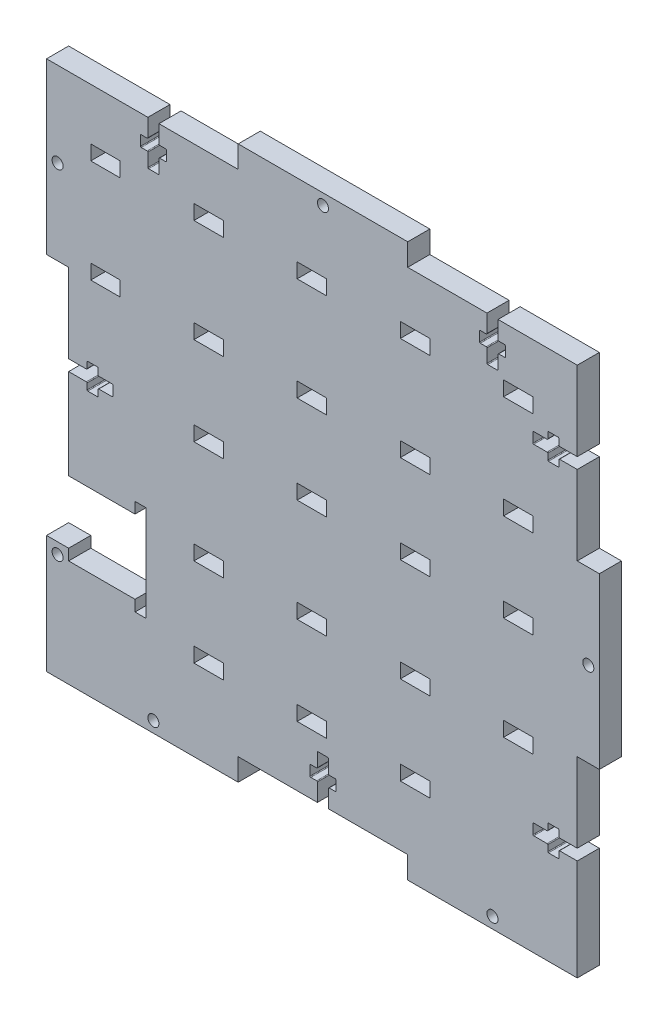
SolidWorks part; units mm, degrees
ref_plane "Front Plane" through (0, 0, 0) normal (0, 0, 1) x (1, 0, 0)
ref_plane "Top Plane" through (0, 0, 0) normal (0, 1, 0) x (1, 0, 0)
ref_plane "Right Plane" through (0, 0, 0) normal (1, 0, 0) x (0, 0, -1)
sketch "Sketch1" plane through (0, 0, 0) normal (0, 0, 1) x (1, 0, 0)
  line L0 (-69, 69) -> (-23, 69)
  line L5 (-75, -75) -> (75, -75) construction
  line L6 (-75, -75) -> (-75, 75) construction
  line L7 (-75, 75) -> (75, 75) construction
  line L8 (75, -75) -> (75, 75) construction
  line L9 (75, 23) -> (69, 23)
  line L10 (69, -23) -> (75, -23)
  line L11 (-69, -69) -> (69, -69) construction
  line L12 (-69, -69) -> (-69, 69) construction
  line L13 (-69, 69) -> (69, 69) construction
  line L14 (69, -69) -> (69, 69) construction
  line L15 (-69, -69) -> (69, 69) construction
  line L16 (69, -69) -> (69, -23)
  line L17 (-23, 69) -> (-23, 75)
  line L18 (-23, 75) -> (23, 75)
  line L19 (23, 75) -> (23, 69)
  line L20 (23, 69) -> (69, 69)
  line L21 (75, -23) -> (75, 23)
  line L22 (69, 23) -> (69, 69)
  line L23 (-75, 23) -> (-69, 23)
  line L24 (-69, 69) -> (-75, 69)
  line L25 (-75, 69) -> (-75, 23)
  line L26 (69, -69) -> (69, -75)
  line L27 (69, -75) -> (23, -75)
  line L28 (23, -75) -> (23, -69)
  line L29 (23, -69) -> (-23, -69)
  line L30 (-23, -69) -> (-23, -75)
  line L31 (-23, -75) -> (-69, -75)
  line L32 (-69, -75) -> (-69, -69) construction
  line L33 (-69, 23) -> (-69, -23)
  line L34 (-69, -23) -> (-75, -23)
  line L35 (-75, -23) -> (-75, -69)
  line L36 (-75, -69) -> (-69, -69) construction
  line L37 (-46, 69) -> (-46, -75) construction
  line L38 (-69, 69) -> (69, -69) construction
  line L39 (-75, -75) -> (-69, -75)
  line L40 (-75, -75) -> (-75, -69)
  point P0 (0, 0)
  point P6 (-7, -7)
  point P26 (0, -75)
  point P27 (-75, 0)
  dimension "D1" = 150
  dimension "D2" = 150
  dimension "D5" = 46
  dimension "D3" = 6
  dimension "D6" = 6
  dimension "D7" = 6
extrude "Box Side" add sketch "Sketch1" along normal blind 6
sketch "Sketch2" plane through (0, 0, 6) normal (0, 0, 1) x (1, 0, 0)
  line L0 (23, 72) -> (-23, 72) construction
  line L1 (23, 75) -> (23, 69) construction
  line L2 (-23, 69) -> (-23, 75) construction
  line L3 (-46, 69) -> (-46, -75) construction
  line L5 (0, 75) -> (0, 69) construction
  line L6 (-23, 75) -> (23, 75) construction
  line L7 (-69, 69) -> (69, 69) construction
  line L16 (-46, 69) -> (-46, -75) construction
  line L21 (0, -69) -> (0, 69) construction
  line L35 (-69, 69) -> (-23, 69) construction
  line L36 (-44.5, 69) -> (-44.5, 64.2)
  line L37 (-44.3, 64) -> (-42.7, 64)
  line L38 (-42.5, 63.8) -> (-42.5, 61.2)
  line L39 (-42.7, 61) -> (-44.3, 61)
  line L40 (-44.5, 60.8) -> (-44.5, 57.2)
  line L46 (-44.7, 57) -> (-47.3, 57)
  line L48 (-44.5, 69) -> (-47.5, 69)
  line L51 (-47.5, 60.8) -> (-47.5, 57.2)
  line L52 (-49.3, 61) -> (-47.7, 61)
  line L53 (-49.5, 63.8) -> (-49.5, 61.2)
  line L54 (-47.7, 64) -> (-49.3, 64)
  line L55 (-47.5, 69) -> (-47.5, 64.2)
  line L56 (47.5, 69) -> (47.5, 64.2)
  line L57 (47.7, 64) -> (49.3, 64)
  line L58 (49.5, 63.8) -> (49.5, 61.2)
  line L59 (49.3, 61) -> (47.7, 61)
  line L60 (47.5, 60.8) -> (47.5, 57.2)
  line L61 (44.5, 69) -> (47.5, 69)
  line L62 (44.7, 57) -> (47.3, 57)
  line L63 (44.5, 60.8) -> (44.5, 57.2)
  line L64 (42.7, 61) -> (44.3, 61)
  line L65 (42.5, 63.8) -> (42.5, 61.2)
  line L66 (44.3, 64) -> (42.7, 64)
  line L67 (44.5, 69) -> (44.5, 64.2)
  line L68 (-69, -69) -> (69, 69) construction
  line L69 (-69, -69) -> (69, 69) construction
  line L70 (75, 0) -> (69, 0) construction
  line L71 (72, 23) -> (72, -23) construction
  line L72 (69, 44.5) -> (64.2, 44.5)
  line L73 (64, 44.3) -> (64, 42.7)
  line L74 (63.8, 42.5) -> (61.2, 42.5)
  line L75 (61, 42.7) -> (61, 44.3)
  line L76 (60.8, 44.5) -> (57.2, 44.5)
  line L77 (57, 44.7) -> (57, 47.3)
  line L78 (69, 44.5) -> (69, 47.5)
  line L79 (60.8, 47.5) -> (57.2, 47.5)
  line L80 (61, 49.3) -> (61, 47.7)
  line L81 (63.8, 49.5) -> (61.2, 49.5)
  line L82 (64, 47.7) -> (64, 49.3)
  line L83 (69, 47.5) -> (64.2, 47.5)
  line L84 (69, -47.5) -> (64.2, -47.5)
  line L85 (64, -47.7) -> (64, -49.3)
  line L86 (63.8, -49.5) -> (61.2, -49.5)
  line L87 (61, -49.3) -> (61, -47.7)
  line L88 (60.8, -47.5) -> (57.2, -47.5)
  line L89 (69, -44.5) -> (69, -47.5)
  line L90 (57, -44.7) -> (57, -47.3)
  line L91 (60.8, -44.5) -> (57.2, -44.5)
  line L92 (61, -42.7) -> (61, -44.3)
  line L93 (63.8, -42.5) -> (61.2, -42.5)
  line L94 (64, -44.3) -> (64, -42.7)
  line L95 (69, -44.5) -> (64.2, -44.5)
  line L120 (-69, 69) -> (69, -69) construction
  line L121 (-69, 69) -> (69, -69) construction
  line L122 (-1.5, -69) -> (1.5, -69)
  line L123 (-23, -69) -> (23, -69) construction
  line L124 (1.5, -69) -> (1.5, -64.2)
  line L125 (1.7, -64) -> (3.3, -64)
  line L126 (3.5, -63.8) -> (3.5, -61.2)
  line L127 (3.3, -61) -> (1.7, -61)
  line L128 (1.5, -60.8) -> (1.5, -57.2)
  line L129 (1.3, -57) -> (-1.3, -57)
  line L130 (-1.5, -60.8) -> (-1.5, -57.2)
  line L131 (-3.3, -61) -> (-1.7, -61)
  line L132 (-3.5, -63.8) -> (-3.5, -61.2)
  line L133 (-1.7, -64) -> (-3.3, -64)
  line L134 (-1.5, -69) -> (-1.5, -64.2)
  line L135 (-69, -1.5) -> (-64.2, -1.5)
  line L136 (-64, -1.7) -> (-64, -3.3)
  line L137 (-63.8, -3.5) -> (-61.2, -3.5)
  line L138 (-61, -3.3) -> (-61, -1.7)
  line L139 (-60.8, -1.5) -> (-57.2, -1.5)
  line L140 (-57, 1.3) -> (-57, -1.3)
  line L141 (-60.8, 1.5) -> (-57.2, 1.5)
  line L142 (-61, 3.3) -> (-61, 1.7)
  line L143 (-63.8, 3.5) -> (-61.2, 3.5)
  line L144 (-64, 1.7) -> (-64, 3.3)
  line L145 (-69, 1.5) -> (-64.2, 1.5)
  line L146 (-69, -1.5) -> (-69, 1.5)
  line L147 (-69, -72) -> (-23, -72) construction
  line L148 (-23, 69) -> (-75, 69) construction
  line L149 (-23, -75) -> (-23, -69) construction
  line L150 (-69, -69) -> (-69, -75) construction
  line L151 (-75, -75) -> (-23, -75) construction
  circle A0 centre (0, 72) radius 1.5
  arc A1 (-44.5, 57.2) -> (-44.7, 57) centre (-44.7, 57.2) cw
  arc A2 (-44.3, 61) -> (-44.5, 60.8) centre (-44.3, 60.8) ccw
  arc A3 (-42.5, 61.2) -> (-42.7, 61) centre (-42.7, 61.2) cw
  arc A4 (-42.7, 64) -> (-42.5, 63.8) centre (-42.7, 63.8) cw
  arc A5 (-44.5, 64.2) -> (-44.3, 64) centre (-44.3, 64.2) ccw
  arc A6 (-47.5, 64.2) -> (-47.7, 64) centre (-47.7, 64.2) cw
  arc A7 (-49.3, 64) -> (-49.5, 63.8) centre (-49.3, 63.8) ccw
  arc A8 (-49.5, 61.2) -> (-49.3, 61) centre (-49.3, 61.2) ccw
  arc A9 (-47.7, 61) -> (-47.5, 60.8) centre (-47.7, 60.8) cw
  arc A10 (-47.5, 57.2) -> (-47.3, 57) centre (-47.3, 57.2) ccw
  arc A11 (47.5, 57.2) -> (47.3, 57) centre (47.3, 57.2) cw
  arc A12 (47.7, 61) -> (47.5, 60.8) centre (47.7, 60.8) ccw
  arc A13 (49.5, 61.2) -> (49.3, 61) centre (49.3, 61.2) cw
  arc A14 (49.3, 64) -> (49.5, 63.8) centre (49.3, 63.8) cw
  arc A15 (47.5, 64.2) -> (47.7, 64) centre (47.7, 64.2) ccw
  arc A16 (44.5, 64.2) -> (44.3, 64) centre (44.3, 64.2) cw
  arc A17 (42.7, 64) -> (42.5, 63.8) centre (42.7, 63.8) ccw
  arc A18 (42.5, 61.2) -> (42.7, 61) centre (42.7, 61.2) ccw
  arc A19 (44.3, 61) -> (44.5, 60.8) centre (44.3, 60.8) cw
  arc A20 (44.5, 57.2) -> (44.7, 57) centre (44.7, 57.2) ccw
  arc A21 (57.2, 44.5) -> (57, 44.7) centre (57.2, 44.7) cw
  arc A22 (61, 44.3) -> (60.8, 44.5) centre (60.8, 44.3) ccw
  arc A23 (61.2, 42.5) -> (61, 42.7) centre (61.2, 42.7) cw
  arc A24 (64, 42.7) -> (63.8, 42.5) centre (63.8, 42.7) cw
  arc A25 (64.2, 44.5) -> (64, 44.3) centre (64.2, 44.3) ccw
  arc A26 (64.2, 47.5) -> (64, 47.7) centre (64.2, 47.7) cw
  arc A27 (64, 49.3) -> (63.8, 49.5) centre (63.8, 49.3) ccw
  arc A28 (61.2, 49.5) -> (61, 49.3) centre (61.2, 49.3) ccw
  arc A29 (61, 47.7) -> (60.8, 47.5) centre (60.8, 47.7) cw
  arc A30 (57.2, 47.5) -> (57, 47.3) centre (57.2, 47.3) ccw
  arc A31 (57.2, -47.5) -> (57, -47.3) centre (57.2, -47.3) cw
  arc A32 (61, -47.7) -> (60.8, -47.5) centre (60.8, -47.7) ccw
  arc A33 (61.2, -49.5) -> (61, -49.3) centre (61.2, -49.3) cw
  arc A34 (64, -49.3) -> (63.8, -49.5) centre (63.8, -49.3) cw
  arc A35 (64.2, -47.5) -> (64, -47.7) centre (64.2, -47.7) ccw
  arc A36 (64.2, -44.5) -> (64, -44.3) centre (64.2, -44.3) cw
  arc A37 (64, -42.7) -> (63.8, -42.5) centre (63.8, -42.7) ccw
  arc A38 (61.2, -42.5) -> (61, -42.7) centre (61.2, -42.7) ccw
  arc A39 (61, -44.3) -> (60.8, -44.5) centre (60.8, -44.3) cw
  arc A40 (57.2, -44.5) -> (57, -44.7) centre (57.2, -44.7) ccw
  circle A41 centre (72, 0) radius 1.5
  arc A62 (1.5, -57.2) -> (1.3, -57) centre (1.3, -57.2) ccw
  arc A63 (1.7, -61) -> (1.5, -60.8) centre (1.7, -60.8) cw
  arc A64 (3.5, -61.2) -> (3.3, -61) centre (3.3, -61.2) ccw
  arc A65 (3.3, -64) -> (3.5, -63.8) centre (3.3, -63.8) ccw
  arc A66 (1.5, -64.2) -> (1.7, -64) centre (1.7, -64.2) cw
  arc A67 (-1.5, -64.2) -> (-1.7, -64) centre (-1.7, -64.2) ccw
  arc A68 (-3.3, -64) -> (-3.5, -63.8) centre (-3.3, -63.8) cw
  arc A69 (-3.5, -61.2) -> (-3.3, -61) centre (-3.3, -61.2) cw
  arc A70 (-1.7, -61) -> (-1.5, -60.8) centre (-1.7, -60.8) ccw
  arc A71 (-1.5, -57.2) -> (-1.3, -57) centre (-1.3, -57.2) cw
  arc A72 (-57.2, -1.5) -> (-57, -1.3) centre (-57.2, -1.3) ccw
  arc A73 (-61, -1.7) -> (-60.8, -1.5) centre (-60.8, -1.7) cw
  arc A74 (-61.2, -3.5) -> (-61, -3.3) centre (-61.2, -3.3) ccw
  arc A75 (-64, -3.3) -> (-63.8, -3.5) centre (-63.8, -3.3) ccw
  arc A76 (-64.2, -1.5) -> (-64, -1.7) centre (-64.2, -1.7) cw
  arc A77 (-64.2, 1.5) -> (-64, 1.7) centre (-64.2, 1.7) ccw
  arc A78 (-64, 3.3) -> (-63.8, 3.5) centre (-63.8, 3.3) cw
  arc A79 (-61.2, 3.5) -> (-61, 3.3) centre (-61.2, 3.3) cw
  arc A80 (-61, 1.7) -> (-60.8, 1.5) centre (-60.8, 1.7) ccw
  arc A81 (-57.2, 1.5) -> (-57, 1.3) centre (-57.2, 1.3) cw
  circle A82 centre (-46, -72) radius 1.5
  circle A83 centre (46, -72) radius 1.5
  circle A84 centre (-72, 46) radius 1.5
  circle A85 centre (-72, -46) radius 1.5
  point P6 (0, 72)
  point P38 (0, 0)
  point P56 (-46, 57)
  point P88 (46, 57)
  point P161 (57, 46)
  point P162 (57, -46)
  point P198 (0, -57)
  point P231 (-57, 0)
  point P234 (-42.5, 62.5)
  dimension "D1" = 3
  dimension "D2" = 0.2
  dimension "D8" = 0.2
  dimension "D14" = 3
  dimension "D4" = 3
  dimension "D7" = 1.5
  dimension "D10" = 3
  dimension "D12" = 1.5
  dimension "D9" = 12
  dimension "D11" = 5
  dimension "D13" = 7
  dimension "D3" = 12
  dimension "D5" = 7
  dimension "D6" = 5
extrude "Screw Cut-outs" cut sketch "Sketch2" against normal through all
sketch "Sketch3" plane through (0, 0, 6) normal (0, 0, 1) x (1, 0, 0)
  line L0 (-75, -75) -> (-23, -75) construction
  line L1 (-75, -49) -> (-48, -49)
  line L2 (-75, -49) -> (-75, -23)
  line L3 (-75, -23) -> (-48, -23)
  line L4 (-48, -49) -> (-48, -23)
  line L5 (-75, -23) -> (-75, -75) construction
  line L6 (-75, -46) -> (-48, -46)
  line L7 (-75, -26) -> (-48, -26)
  line L9 (-75, -26) -> (-69, -26)
  line L10 (-75, -26) -> (-75, -29)
  line L11 (-75, -29) -> (-69, -29)
  line L12 (-69, -26) -> (-69, -29)
  line L13 (-75, -46) -> (-69, -46)
  line L14 (-75, -46) -> (-75, -43)
  line L15 (-75, -43) -> (-69, -43)
  line L16 (-69, -46) -> (-69, -43)
  line L17 (-69, -26) -> (-75, -26)
  line L18 (-69, -26) -> (-69, -23)
  line L19 (-69, -23) -> (-75, -23)
  line L20 (-75, -26) -> (-75, -23)
  line L25 (-48, -23) -> (-51, -23)
  line L26 (-48, -23) -> (-48, -26)
  line L27 (-48, -26) -> (-51, -26)
  line L28 (-51, -23) -> (-51, -26)
  line L29 (-48, -46) -> (-51, -46)
  line L30 (-48, -46) -> (-48, -49)
  line L31 (-48, -49) -> (-51, -49)
  line L32 (-51, -46) -> (-51, -49)
  dimension "D1" = 26
  dimension "D2" = 27
  dimension "D3" = 26
  dimension "D4" = 20
  dimension "D5" = 3
  dimension "D6" = 3
  dimension "D7" = 6
  dimension "D8" = 3
  dimension "D9" = 3
extrude "Cut-Extrude1" cut sketch "Sketch3" against normal through all contours L7 L2 L6 L4 | L10 L9 L12 L11 | L18 L17 L20 L19 | L26 L25 L28 L27 | L30 L29 L32 L31 region at (-60.75, -36, 6)
sketch "Sketch4" plane through (0, 0, 6) normal (0, 0, 1) x (1, 0, 0)
  line L0 (-27, 55) -> (-27, 51)
  line L1 (-63, 55) -> (-55, 55)
  line L2 (-63, 55) -> (-63, 51)
  line L3 (-63, 51) -> (-55, 51)
  line L4 (-55, 55) -> (-55, 51)
  line L5 (-59, 53) -> (-31, 53) construction
  line L6 (-59, 53) -> (-59, 25) construction
  line L7 (-59, 25) -> (-31, 25) construction
  line L8 (-31, 53) -> (-31, 25) construction
  line L9 (-59, 53) -> (-31, 25) construction
  line L10 (-59, 25) -> (-31, 53) construction
  line L11 (-35, 55) -> (-27, 55)
  line L12 (-35, 55) -> (-35, 51)
  line L13 (-35, 51) -> (-27, 51)
  line L14 (-27, 27) -> (-27, 23)
  line L15 (-35, 27) -> (-27, 27)
  line L16 (-35, 27) -> (-35, 23)
  line L17 (-35, 23) -> (-27, 23)
  line L18 (-55, 27) -> (-55, 23)
  line L19 (-63, 27) -> (-55, 27)
  line L20 (-63, 27) -> (-63, 23)
  line L21 (-63, 23) -> (-55, 23)
  line L22 (-47.5, 69) -> (-75, 69) construction
  line L23 (-75, 69) -> (-75, 23) construction
  line L24 (21, 23.2836) -> (29, 23.2836)
  line L25 (21, 27.2836) -> (29, 27.2836)
  line L26 (21, 27.2836) -> (21, 23.2836)
  line L27 (29, 27.2836) -> (29, 23.2836)
  line L28 (1, 27.2836) -> (1, 23.2836)
  line L29 (-7, 23.2836) -> (1, 23.2836)
  line L30 (-7, 27.2836) -> (-7, 23.2836)
  line L31 (-7, 27.2836) -> (1, 27.2836)
  line L32 (-7, 51.2836) -> (1, 51.2836)
  line L33 (-7, 55.2836) -> (-7, 51.2836)
  line L34 (-7, 55.2836) -> (1, 55.2836)
  line L35 (1, 55.2836) -> (1, 51.2836)
  line L36 (29, 55.2836) -> (29, 51.2836)
  line L37 (21, 51.2836) -> (29, 51.2836)
  line L38 (21, 55.2836) -> (29, 55.2836)
  line L39 (21, 55.2836) -> (21, 51.2836)
  line L44 (57, 27.5671) -> (57, 23.5671)
  line L45 (49, 23.5671) -> (57, 23.5671)
  line L46 (49, 27.5671) -> (49, 23.5671)
  line L47 (49, 27.5671) -> (57, 27.5671)
  line L48 (49, 51.5671) -> (57, 51.5671)
  line L49 (49, 55.5671) -> (49, 51.5671)
  line L50 (49, 55.5671) -> (57, 55.5671)
  line L51 (57, 55.5671) -> (57, 51.5671)
  line L56 (21, -28.7164) -> (29, -28.7164)
  line L57 (21, -24.7164) -> (29, -24.7164)
  line L58 (21, -24.7164) -> (21, -28.7164)
  line L59 (29, -24.7164) -> (29, -28.7164)
  line L60 (1, -24.7164) -> (1, -28.7164)
  line L61 (-7, -28.7164) -> (1, -28.7164)
  line L62 (-7, -24.7164) -> (-7, -28.7164)
  line L63 (-7, -24.7164) -> (1, -24.7164)
  line L64 (-7, -0.7164) -> (1, -0.7164)
  line L65 (-7, 3.2836) -> (-7, -0.7164)
  line L66 (-7, 3.2836) -> (1, 3.2836)
  line L67 (1, 3.2836) -> (1, -0.7164)
  line L68 (29, 3.2836) -> (29, -0.7164)
  line L69 (21, -0.7164) -> (29, -0.7164)
  line L70 (21, 3.2836) -> (29, 3.2836)
  line L71 (21, 3.2836) -> (21, -0.7164)
  line L76 (57, -24.4329) -> (57, -28.4329)
  line L77 (49, -28.4329) -> (57, -28.4329)
  line L78 (49, -24.4329) -> (49, -28.4329)
  line L79 (49, -24.4329) -> (57, -24.4329)
  line L80 (49, -0.4329) -> (57, -0.4329)
  line L81 (49, 3.5671) -> (49, -0.4329)
  line L82 (49, 3.5671) -> (57, 3.5671)
  line L83 (57, 3.5671) -> (57, -0.4329)
  line L96 (-7, -52.7164) -> (1, -52.7164)
  line L97 (-7, -48.7164) -> (-7, -52.7164)
  line L98 (-7, -48.7164) -> (1, -48.7164)
  line L99 (1, -48.7164) -> (1, -52.7164)
  line L100 (29, -48.7164) -> (29, -52.7164)
  line L101 (21, -52.7164) -> (29, -52.7164)
  line L102 (21, -48.7164) -> (29, -48.7164)
  line L103 (21, -48.7164) -> (21, -52.7164)
  line L112 (49, -52.4329) -> (57, -52.4329) construction
  line L113 (49, -48.4329) -> (49, -52.4329) construction
  line L114 (49, -48.4329) -> (57, -48.4329) construction
  line L115 (57, -48.4329) -> (57, -52.4329) construction
  line L120 (-35, -29) -> (-27, -29)
  line L121 (-35, -25) -> (-27, -25)
  line L122 (-35, -25) -> (-35, -29)
  line L123 (-27, -25) -> (-27, -29)
  line L124 (-55, -25) -> (-55, -29) construction
  line L125 (-63, -29) -> (-55, -29) construction
  line L126 (-63, -25) -> (-63, -29) construction
  line L127 (-63, -25) -> (-55, -25) construction
  line L128 (-63, -1) -> (-55, -1) construction
  line L129 (-63, 3) -> (-63, -1) construction
  line L130 (-63, 3) -> (-55, 3) construction
  line L131 (-55, 3) -> (-55, -1) construction
  line L132 (-27, 3) -> (-27, -1)
  line L133 (-35, -1) -> (-27, -1)
  line L134 (-35, 3) -> (-27, 3)
  line L135 (-35, 3) -> (-35, -1)
  line L144 (-63, -53) -> (-55, -53) construction
  line L145 (-63, -49) -> (-63, -53) construction
  line L146 (-63, -49) -> (-55, -49) construction
  line L147 (-55, -49) -> (-55, -53) construction
  line L148 (-27, -49) -> (-27, -53)
  line L149 (-35, -53) -> (-27, -53)
  line L150 (-35, -49) -> (-27, -49)
  line L151 (-35, -49) -> (-35, -53)
  line L152 (21, -80.7164) -> (29, -80.7164) [skipped]
  line L153 (21, -76.7164) -> (29, -76.7164) [skipped]
  line L154 (21, -76.7164) -> (21, -80.7164) [skipped]
  line L155 (29, -76.7164) -> (29, -80.7164) [skipped]
  line L156 (1, -76.7164) -> (1, -80.7164) [skipped]
  line L157 (-7, -80.7164) -> (1, -80.7164) [skipped]
  line L158 (-7, -76.7164) -> (-7, -80.7164) [skipped]
  line L159 (-7, -76.7164) -> (1, -76.7164) [skipped]
  line L160 (77, -80.4329) -> (85, -80.4329) [skipped]
  line L161 (77, -76.4329) -> (85, -76.4329) [skipped]
  line L162 (77, -76.4329) -> (77, -80.4329) [skipped]
  line L163 (85, -76.4329) -> (85, -80.4329) [skipped]
  line L164 (57, -76.4329) -> (57, -80.4329) [skipped]
  line L165 (49, -80.4329) -> (57, -80.4329) [skipped]
  line L166 (49, -76.4329) -> (49, -80.4329) [skipped]
  line L167 (49, -76.4329) -> (57, -76.4329) [skipped]
  line L168 (-35, -81) -> (-27, -81) [skipped]
  line L169 (-35, -77) -> (-27, -77) [skipped]
  line L170 (-35, -77) -> (-35, -81) [skipped]
  line L171 (-27, -77) -> (-27, -81) [skipped]
  line L172 (-55, -77) -> (-55, -81) [skipped]
  line L173 (-63, -81) -> (-55, -81) [skipped]
  line L174 (-63, -77) -> (-63, -81) [skipped]
  line L175 (-63, -77) -> (-55, -77) [skipped]
  line L176 (77, 23.5671) -> (85, 23.5671) [skipped]
  line L177 (77, 27.5671) -> (85, 27.5671) [skipped]
  line L178 (77, 27.5671) -> (77, 23.5671) [skipped]
  line L179 (85, 27.5671) -> (85, 23.5671) [skipped]
  line L180 (85, 55.5671) -> (85, 51.5671) [skipped]
  line L181 (77, 51.5671) -> (85, 51.5671) [skipped]
  line L182 (77, 55.5671) -> (85, 55.5671) [skipped]
  line L183 (77, 55.5671) -> (77, 51.5671) [skipped]
  line L184 (77, -28.4329) -> (85, -28.4329) [skipped]
  line L185 (77, -24.4329) -> (85, -24.4329) [skipped]
  line L186 (77, -24.4329) -> (77, -28.4329) [skipped]
  line L187 (85, -24.4329) -> (85, -28.4329) [skipped]
  line L188 (85, 3.5671) -> (85, -0.4329) [skipped]
  line L189 (77, -0.4329) -> (85, -0.4329) [skipped]
  line L190 (77, 3.5671) -> (85, 3.5671) [skipped]
  line L191 (77, 3.5671) -> (77, -0.4329) [skipped]
  line L192 (85, -48.4329) -> (85, -52.4329) [skipped]
  line L193 (77, -52.4329) -> (85, -52.4329) [skipped]
  line L194 (77, -48.4329) -> (85, -48.4329) [skipped]
  line L195 (77, -48.4329) -> (77, -52.4329) [skipped]
  circle A0 centre (-59, 53) radius 2 construction
  point P6 (-59, 51)
  point P7 (-63, 25)
  point P8 (-59, 23)
  point P12 (-45, 39)
  point P13 (-31, 23)
  point P26 (-7.699, 47.2598)
  point P27 (-21.1237, -1.5841)
  point P33 (-31, 51)
  point P41 (-59, 27)
  point P43 (0, 0)
  point P164 (-55.3166, -13)
  dimension "D1" = 8
  dimension "D2" = 4
  dimension "D3" = 2
  dimension "D5" = 28
  dimension "D6" = 16
  dimension "D7" = 16
  dimension "D10" = 20
  dimension "D11" = 20
  dimension "D4" = 2
  dimension "D8" = 3
  dimension "D9" = 3
extrude "Cut-Extrude2" cut sketch "Sketch4" against normal through all
equation "\"filletRadius\"=0.2"
equation "\"D8@Sketch2\"=\"filletRadius\""
equation "\"D2@Sketch2\"=\"filletRadius\""
equation "\"fingerWidth\"= 46"
equation "\"D5@Sketch1\"=\"fingerWidth\""
equation "\"wallThickness\"= 6"
equation "\"D3@Sketch1\" = \"wallThickness\""
equation "\"D6@Sketch1\" = \"wallThickness\""
equation "\"D7@Sketch1\" = \"wallThickness\""
equation "\"D1@Box Side\" = \"wallThickness\""
equation "\"M3\"= 3"
equation "\"D14@Sketch2\"=\"M3\""
equation "\"D1@Sketch2\"=\"M3\""
equation "\"D12@Sketch2\"=\"M3\"/2"
equation "\"nutThickness\"=3"
equation "\"D10@Sketch2\" = \"nutThickness\""
equation "\"boltLength\"= 12"
equation "\"D9@Sketch2\" = \"boltLength\""
equation "\"distanceToNut\"= 5"
equation "\"D11@Sketch2\" = \"distanceToNut\""
equation "\"D13@Sketch2\" = \"nutWidth\""
equation "\"D7@Sketch2\"=\"M3\"/2"
equation "\"D4@Sketch2\" = \"nutThickness\""
equation "\"D3@Sketch2\" = \"boltLength\""
equation "\"D5@Sketch2\" = \"nutWidth\""
equation "\"D6@Sketch2\" = \"distanceToNut\""
equation "\"sideLength\"=150"
equation "\"D1@Sketch1\"=\"sideLength\""
equation "\"D2@Sketch1\"=\"sideLength\""
equation "\"nutWidth\"=7"
